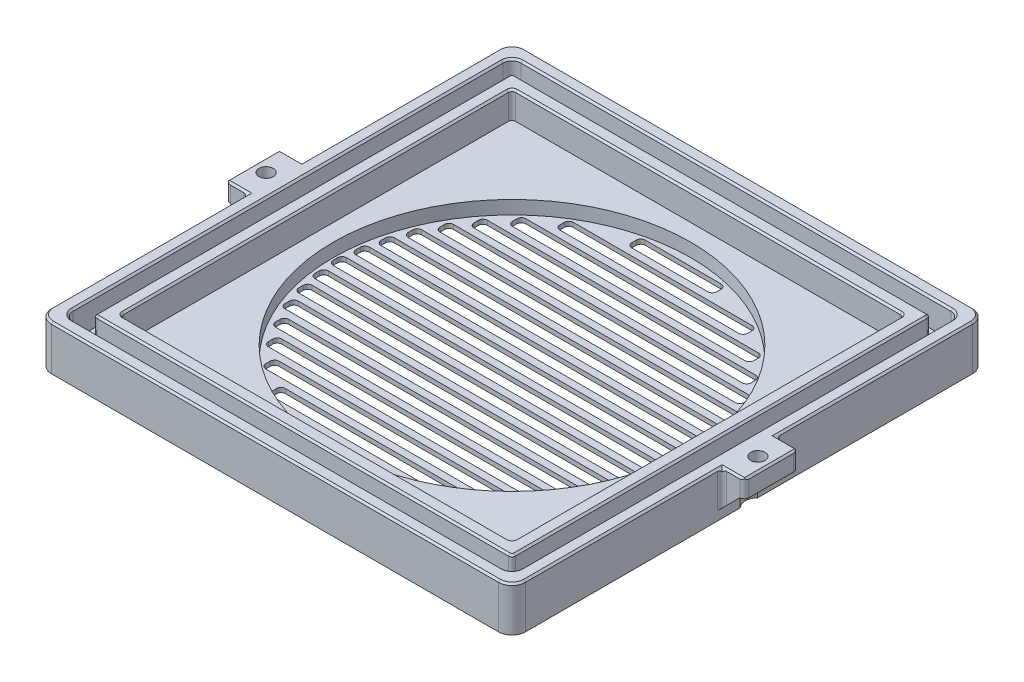
SolidWorks part; units mm, degrees
ref_plane "前视基准面" through (0, 0, 0) normal (0, 0, 1) x (1, 0, 0)
ref_plane "上视基准面" through (0, 0, 0) normal (0, 1, 0) x (1, 0, 0)
ref_plane "右视基准面" through (0, 0, 0) normal (1, 0, 0) x (0, 0, -1)
other "Configuration Table"
sketch "草图1" plane through (0, 0, 0) normal (0, 1, 0) x (1, 0, 0)
  line L1 (0, 0) -> (106, 0)
  line L2 (0, 0) -> (0, 106)
  line L3 (0, 106) -> (106, 106)
  line L4 (106, 0) -> (106, 106)
  dimension "D1" = 106
  dimension "D2" = 106
extrude "凸台-拉伸1" add sketch "草图1" along normal blind 10
sketch "草图2" plane through (0, 10, 0) normal (0, 1, 0) x (1, 0, 0)
  line L8 (2.9, 103.1) -> (2.9, 2.9)
  line L9 (2.9, 2.9) -> (103.1, 2.9)
  line L10 (103.1, 2.9) -> (103.1, 103.1)
  line L11 (103.1, 103.1) -> (2.9, 103.1)
  line L12 (2.9, 103.1) -> (2.9, 2.9)
  line L13 (2.9, 2.9) -> (103.1, 2.9)
  line L14 (103.1, 2.9) -> (103.1, 103.1)
  line L15 (103.1, 103.1) -> (2.9, 103.1)
  line L20 (6.2, 99.8) -> (6.2, 6.2)
  line L21 (6.2, 6.2) -> (99.8, 6.2)
  line L22 (99.8, 6.2) -> (99.8, 99.8)
  line L23 (99.8, 99.8) -> (6.2, 99.8)
  line L24 (6.2, 99.8) -> (6.2, 6.2)
  line L25 (6.2, 6.2) -> (99.8, 6.2)
  line L26 (99.8, 6.2) -> (99.8, 99.8)
  line L27 (99.8, 99.8) -> (6.2, 99.8)
  dimension "D1" = 2.9
  dimension "D2" = 6.2
extrude "切除-拉伸1" cut sketch "草图2" against normal blind 6
sketch "草图3" plane through (0, 10, 0) normal (0, 1, 0) x (1, 0, 0)
  line L8 (96.8, 96.8) -> (9.2, 96.8)
  line L9 (9.2, 96.8) -> (9.2, 9.2)
  line L10 (9.2, 9.2) -> (96.8, 9.2)
  line L11 (96.8, 9.2) -> (96.8, 96.8)
  line L12 (96.8, 96.8) -> (9.2, 96.8)
  line L13 (9.2, 96.8) -> (9.2, 9.2)
  line L14 (9.2, 9.2) -> (96.8, 9.2)
  line L15 (96.8, 9.2) -> (96.8, 96.8)
  dimension "D1" = 3
extrude "切除-拉伸3" cut sketch "草图3" against normal blind 6
sketch "草图4" plane through (0, 4, 0) normal (0, -1, 0) x (-1, 0, 0)
  line L0 (0, 0) -> (-106, 0) construction
  line L1 (0, 106) -> (0, 0) construction
  circle A0 centre (-53, 53) radius 40
  point P4 (-53, 0)
  point P7 (0, 53)
  dimension "D3" = 80
  dimension "D1" = 0
  dimension "D2" = 0
extrude "切除-拉伸4" cut sketch "草图4" along normal blind 3
fillet "圆角1" radius 2 4 edges at (103.1, 7, -103.1) (2.9, 7, -103.1) (2.9, 7, -2.9) (103.1, 7, -2.9)
fillet "圆角2" radius 3 4 edges at (106, 5, -106) (0, 5, -106) (0, 5, 0) (106, 5, 0)
fillet "圆角3" radius 0.8 8 edges at (99.8, 7, -99.8) (6.2, 7, -99.8) (6.2, 7, -6.2) (99.8, 7, -6.2) (9.2, 7, -9.2) (9.2, 7, -96.8) (96.8, 7, -96.8) (96.8, 7, -9.2)
sketch "草图6" plane through (0, 10, 0) normal (0, 1, 0) x (1, 0, 0)
  line L0 (0, 103) -> (0, 3) construction
  line L1 (0, 47) -> (-5, 47)
  line L2 (0, 47) -> (0, 59)
  line L3 (0, 59) -> (-5, 59)
  line L4 (-5, 47) -> (-5, 59)
  line L5 (106, 3) -> (106, 103) construction
  line L6 (106, 59) -> (111, 59)
  line L7 (106, 59) -> (106, 47)
  line L8 (106, 47) -> (111, 47)
  line L9 (111, 59) -> (111, 47)
  point P6 (0, 53)
  point P7 (0, 53)
  point P14 (106, 53)
  point P15 (106, 53)
  dimension "D1" = 0
  dimension "D2" = 5
  dimension "D3" = 12
  dimension "D4" = 0
  dimension "D5" = 12
  dimension "D6" = 5
extrude "凸台-拉伸3" add sketch "草图6" against normal blind 4
chamfer "倒角1" distance 0.4 angle 45 40 edges at (105.1213, 10, -0.8787) (53, 10, 0) (0.8787, 10, -0.8787) (0, 10, -25) (0, 10, -81) (0.8787, 10, -105.1213) (53, 10, -106) (105.1213, 10, -105.1213) (106, 10, -81) (106, 10, -25) (3.4858, 10, -3.4858) (53, 10, -2.9) (102.5142, 10, -3.4858) (103.1, 10, -53) (102.5142, 10, -102.5142) (53, 10, -103.1) (3.4858, 10, -102.5142) (2.9, 10, -53) (99.5657, 10, -6.4343) (53, 10, -6.2) (6.4343, 10, -6.4343) (6.2, 10, -53) (6.4343, 10, -99.5657) (53, 10, -99.8) (99.5657, 10, -99.5657) (99.8, 10, -53) (9.4343, 10, -96.5657) (9.2, 10, -53) (9.4343, 10, -9.4343) (53, 10, -9.2) (96.5657, 10, -9.4343) (96.8, 10, -53) (96.5657, 10, -96.5657) (53, 10, -96.8) (-2.5, 10, -47) (-5, 10, -53) (-2.5, 10, -59) (108.5, 10, -59) (111, 10, -53) (108.5, 10, -47)
chamfer "倒角2" distance 4 angle 45 2 edges at (106, 6, -53) (0, 6, -53)
sketch "草图7" plane through (0, 6, 0) normal (0, -1, 0) x (-1, 0, 0)
  line L0 (-111, 47) -> (-111, 59) construction
  line L1 (5, 59) -> (5, 47) construction
  circle A0 centre (2, 53) radius 1.6
  circle A1 centre (-108, 53) radius 1.6
  dimension "D1" = 3.2
  dimension "D2" = 3.2
  dimension "D3" = 3
  dimension "D4" = 3
extrude "切除-拉伸6" cut sketch "草图7" against normal blind 4 and the other way through all
sketch "草图8" plane through (0, 6, 0) normal (0, -1, 0) x (-1, 0, 0)
  circle A0 centre (2, 53) radius 2.8
  circle A1 centre (-108, 53) radius 2.8
  dimension "D1" = 5.6
  dimension "D2" = 5.6
extrude "切除-拉伸7" cut sketch "草图8" along normal through all
fillet "圆角4" radius 1 8 edges at (106, 5.8, -47) (106, 5.8, -59) (111, 7.8, -59) (111, 7.8, -47) (0, 5.8, -47) (0, 5.8, -59) (-5, 7.8, -47) (-5, 7.8, -59)
sketch "草图9" plane through (0, 1, 0) normal (0, 1, 0) x (1, 0, 0)
  line L0 (13.5, 53) -> (71.3783, 53) construction
  line L1 (13.5, 54.5) -> (92.5, 54.5)
  line L2 (13.5, 54.5) -> (13.5, 51.5)
  line L3 (13.5, 51.5) -> (92.5, 51.5)
  line L4 (92.5, 54.5) -> (92.5, 51.5)
  line L5 (14, 59.1) -> (92, 59.1)
  line L6 (14, 59.1) -> (14, 56.1)
  line L7 (14, 56.1) -> (92, 56.1)
  line L8 (92, 59.1) -> (92, 56.1)
  line L9 (15, 60.7) -> (91, 60.7)
  line L10 (15, 60.7) -> (15, 63.7)
  line L11 (15, 63.7) -> (91, 63.7)
  line L12 (91, 60.7) -> (91, 63.7)
  line L13 (16.5, 68.3) -> (89.5, 68.3)
  line L14 (16.5, 68.3) -> (16.5, 65.3)
  line L15 (16.5, 65.3) -> (89.5, 65.3)
  line L16 (89.5, 68.3) -> (89.5, 65.3)
  line L17 (19, 72.9) -> (87, 72.9)
  line L18 (19, 72.9) -> (19, 69.9)
  line L19 (19, 69.9) -> (87, 69.9)
  line L20 (87, 72.9) -> (87, 69.9)
  line L21 (22, 77.5) -> (84, 77.5)
  line L22 (22, 77.5) -> (22, 74.5)
  line L23 (22, 74.5) -> (84, 74.5)
  line L24 (84, 77.5) -> (84, 74.5)
  line L25 (26, 82.1) -> (80, 82.1)
  line L26 (26, 82.1) -> (26, 79.1)
  line L27 (26, 79.1) -> (80, 79.1)
  line L28 (80, 82.1) -> (80, 79.1)
  line L29 (32, 86.7) -> (74, 86.7)
  line L30 (32, 86.7) -> (32, 83.7)
  line L31 (32, 83.7) -> (74, 83.7)
  line L32 (74, 86.7) -> (74, 83.7)
  line L33 (43.5, 91.3) -> (62.5, 91.3)
  line L34 (43.5, 91.3) -> (43.5, 88.3)
  line L35 (43.5, 88.3) -> (62.5, 88.3)
  line L36 (62.5, 91.3) -> (62.5, 88.3)
  line L37 (43.5, 17.7) -> (62.5, 17.7)
  line L38 (62.5, 14.7) -> (62.5, 17.7)
  line L39 (43.5, 14.7) -> (62.5, 14.7)
  line L40 (43.5, 14.7) -> (43.5, 17.7)
  line L41 (32, 22.3) -> (74, 22.3)
  line L42 (74, 19.3) -> (74, 22.3)
  line L43 (32, 19.3) -> (74, 19.3)
  line L44 (32, 19.3) -> (32, 22.3)
  line L45 (26, 26.9) -> (80, 26.9)
  line L46 (80, 23.9) -> (80, 26.9)
  line L47 (26, 23.9) -> (80, 23.9)
  line L48 (26, 23.9) -> (26, 26.9)
  line L49 (22, 31.5) -> (84, 31.5)
  line L50 (84, 28.5) -> (84, 31.5)
  line L51 (22, 28.5) -> (84, 28.5)
  line L52 (22, 28.5) -> (22, 31.5)
  line L53 (19, 36.1) -> (87, 36.1)
  line L54 (87, 33.1) -> (87, 36.1)
  line L55 (19, 33.1) -> (87, 33.1)
  line L56 (19, 33.1) -> (19, 36.1)
  line L57 (16.5, 40.7) -> (89.5, 40.7)
  line L58 (89.5, 37.7) -> (89.5, 40.7)
  line L59 (16.5, 37.7) -> (89.5, 37.7)
  line L60 (16.5, 37.7) -> (16.5, 40.7)
  line L61 (15, 42.3) -> (91, 42.3)
  line L62 (91, 45.3) -> (91, 42.3)
  line L63 (15, 45.3) -> (91, 45.3)
  line L64 (15, 45.3) -> (15, 42.3)
  line L65 (14, 49.9) -> (92, 49.9)
  line L66 (92, 46.9) -> (92, 49.9)
  line L67 (14, 46.9) -> (92, 46.9)
  line L68 (14, 46.9) -> (14, 49.9)
  circle A0 centre (53, 53) radius 40 construction
  circle A1 centre (53, 53) radius 40 construction
  point P4 (53, 51.5)
  point P7 (13.5, 53)
  point P14 (53, 56.1)
  point P15 (53, 54.5)
  point P20 (53, 60.7)
  point P21 (53, 59.1)
  point P26 (53, 68.3)
  point P27 (53, 63.7)
  point P32 (53, 69.9)
  point P37 (53, 77.5)
  point P38 (53, 72.9)
  point P43 (53, 82.1)
  point P48 (53, 86.7)
  point P53 (53, 91.3)
  dimension "D1" = 0
  dimension "D2" = 3
  dimension "D3" = 0
  dimension "D4" = 79
  dimension "D5" = 3
  dimension "D6" = 0
  dimension "D7" = 1.6
  dimension "D8" = 78
  dimension "D9" = 3
  dimension "D10" = 0
  dimension "D11" = 1.6
  dimension "D12" = 76
  dimension "D13" = 3
  dimension "D14" = 1.6
  dimension "D15" = 0
  dimension "D16" = 73
  dimension "D17" = 3
  dimension "D18" = 1.6
  dimension "D19" = 0
  dimension "D20" = 68
  dimension "D21" = 3
  dimension "D22" = 1.6
  dimension "D23" = 0
  dimension "D24" = 62
  dimension "D25" = 3
  dimension "D26" = 1.6
  dimension "D27" = 0
  dimension "D28" = 54
  dimension "D29" = 3
  dimension "D30" = 1.6
  dimension "D31" = 0
  dimension "D32" = 42
  dimension "D33" = 1.6
  dimension "D34" = 3
  dimension "D35" = 0
  dimension "D36" = 19
extrude "切除-拉伸8" cut sketch "草图9" against normal blind 10
fillet "圆角5" radius 1 68 edges at (43.5, 0.5, -91.3) (62.5, 0.5, -91.3) (62.5, 0.5, -88.3) (43.5, 0.5, -88.3) (32, 0.5, -86.7) (74, 0.5, -86.7) (74, 0.5, -83.7) (32, 0.5, -83.7) (26, 0.5, -82.1) (80, 0.5, -82.1) (80, 0.5, -79.1) (26, 0.5, -79.1) (22, 0.5, -77.5) (84, 0.5, -77.5) (84, 0.5, -74.5) (22, 0.5, -74.5) (19, 0.5, -72.9) (87, 0.5, -72.9) (87, 0.5, -69.9) (19, 0.5, -69.9) (16.5, 0.5, -68.3) (89.5, 0.5, -68.3) (89.5, 0.5, -65.3) (16.5, 0.5, -65.3) (15, 0.5, -63.7) (91, 0.5, -63.7) (91, 0.5, -60.7) (15, 0.5, -60.7) (92, 0.5, -59.1) (92, 0.5, -56.1) (14, 0.5, -56.1) (92.5, 0.5, -54.5) (92.5, 0.5, -51.5) (13.5, 0.5, -51.5) (14, 0.5, -59.1) (13.5, 0.5, -54.5) (43.5, 0.5, -17.7) (62.5, 0.5, -17.7) (62.5, 0.5, -14.7) (43.5, 0.5, -14.7) (32, 0.5, -22.3) (74, 0.5, -22.3) (74, 0.5, -19.3) (32, 0.5, -19.3) (26, 0.5, -26.9) (80, 0.5, -26.9) (80, 0.5, -23.9) (26, 0.5, -23.9) (22, 0.5, -31.5) (84, 0.5, -31.5) (84, 0.5, -28.5) (22, 0.5, -28.5) (19, 0.5, -36.1) (87, 0.5, -36.1) (87, 0.5, -33.1) (19, 0.5, -33.1) (16.5, 0.5, -40.7) (89.5, 0.5, -40.7) (89.5, 0.5, -37.7) (16.5, 0.5, -37.7) (15, 0.5, -45.3) (91, 0.5, -45.3) (91, 0.5, -42.3) (15, 0.5, -42.3) (14, 0.5, -49.9) (92, 0.5, -49.9) (92, 0.5, -46.9) (14, 0.5, -46.9)
